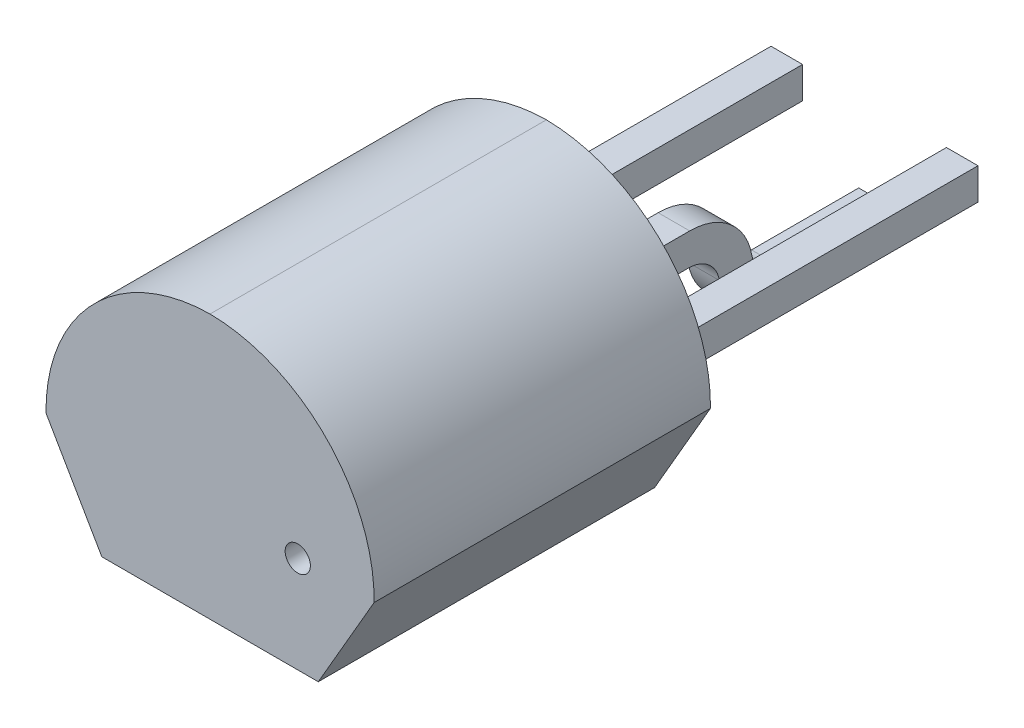
SolidWorks part; units mm, degrees
ref_plane "Спереди" through (0, 0, 0) normal (0, 0, 1) x (1, 0, 0)
ref_plane "Сверху" through (0, 0, 0) normal (0, 1, 0) x (1, 0, 0)
ref_plane "Справа" through (0, 0, 0) normal (1, 0, 0) x (0, 0, -1)
sketch "Эскиз1" plane through (0, 0, 0) normal (0, 0, 1) x (1, 0, 0)
  line L0 (1.14, 0.25) -> (1.64, 0.25)
  line L1 (-0.25, 0.25) -> (0.25, 0.25)
  line L2 (-0.25, 0.25) -> (-0.25, -0.25)
  line L3 (-0.25, -0.25) -> (0.25, -0.25)
  line L4 (0.25, 0.25) -> (0.25, -0.25)
  line L5 (1.14, 0.25) -> (1.14, -0.25)
  line L6 (1.14, -0.25) -> (1.64, -0.25)
  line L7 (1.64, 0.25) -> (1.64, -0.25)
  line L8 (2.53, 0.25) -> (3.03, 0.25)
  line L9 (2.53, 0.25) -> (2.53, -0.25)
  line L10 (2.53, -0.25) -> (3.03, -0.25)
  line L11 (3.03, 0.25) -> (3.03, -0.25)
  line L12 (1.39, 0.25) -> (1.39, -1.8309) construction
  dimension "D1" = 0.5
  dimension "D2" = 0.5
  dimension "D3" = 1.39
ref_plane "Плоскость1" through (0, 0, 2.54) normal (0, 0, 1) x (1, 0, 0)
sketch "Эскиз3" plane through (0, 0, 2.54) normal (0, 0, 1) x (1, 0, 0)
  line L0 (-0.325, -1.53) -> (3.105, -1.53)
  line L6 (-1.21, 0) -> (-0.325, -1.53)
  line L7 (3.99, 0) -> (3.105, -1.53)
  arc A0 (-1.21, 0) -> (1.39, 2.66) centre (1.42, 0.03) cw
  arc A1 (1.39, 2.66) -> (3.99, 0) centre (1.36, 0.03) cw
  dimension "D3" = 2.6302
  dimension "D4" = 2.6302
  dimension "D1" = 5.2
  dimension "D2" = 4.19
  dimension "D5" = 3.43
  dimension "D6" = 1.21
  dimension "D7" = 120.046
extrude "Вытянуть1" add sketch "Эскиз3" along normal blind 5.33
extrude "Вытянуть2" add sketch "Эскиз1" along normal blind 2.54
extrude "Вытянуть3" add sketch "Эскиз1<2>" against normal blind 10.16
sketch "Эскиз1<2>" plane through (0, 0, 0) normal (0, 0, 1) x (1, 0, 0) same geometry as "Эскиз1"
sketch "Эскиз4" plane through (0, 0, 7.87) normal (0, 0, 1) x (1, 0, 0)
  line L0 (1.39, 3.1548) -> (1.39, -1.9485) construction
  line L1 (-1.21, 0) -> (-0.325, -1.53) construction
  line L2 (3.105, -1.53) -> (3.99, 0) construction
  circle A1 centre (2.78, 0) radius 0.2
extrude "Вырез-Вытянуть1" cut sketch "Эскиз4" against normal blind 0.5
sketch "Эскиз5" plane through (0, -0.25, 0) normal (0, 1, 0) x (1, 0, 0)
  line L0 (1.14, -0.04) -> (1.64, -0.04)
  line L4 (1.64, -2.54) -> (1.64, 10.16)
  line L5 (1.64, 10.16) -> (1.14, 10.16)
  line L6 (1.14, 10.16) -> (1.14, -2.54)
  line L7 (1.14, -2.54) -> (1.64, -2.54)
  line L8 (1.64, -0.04) -> (1.64, 10.16)
  line L9 (1.64, 10.16) -> (1.14, 10.16)
  line L10 (1.14, 10.16) -> (1.14, -0.04)
  dimension "D1" = 0
extrude "Вытянуть4" add sketch "Эскиз5" against normal blind 1.25
sketch "Эскиз6" plane through (1.64, 0, 0) normal (1, 0, 0) x (0, 0, -1)
  line L1 (2.46, -1) -> (10.7871, -1)
  line L2 (2.46, -1) -> (0.96, -1)
  line L3 (10.16, -1.5) -> (-0.04, -1.5) construction
  line L4 (10.7871, -1) -> (10.7871, 0.8385)
  line L5 (0.46, -0.5) -> (0.46, 2.1254)
  line L7 (0.46, 2.1254) -> (2.46, 2.1254)
  line L8 (2.46, 2.1254) -> (10.7871, 2.1254)
  line L9 (10.7871, 2.1254) -> (10.7871, 0.8385)
  arc A1 (0.96, -1) -> (0.46, -0.5) centre (0.96, -0.5) cw
  dimension "D2" = 0.5
  dimension "D1" = 0.5
extrude "Вырез-Вытянуть2" cut sketch "Эскиз6" against normal blind 1
fillet "Скругление1" radius 0.5 1 edges at (1.39, -0.25, 0.04)
fillet "Скругление2" radius 1 2 edges at (1.39, -1.5, 0.04) (1.39, 0.25, -0.46)
sketch "Эскиз7" plane through (0, 0, -10.16) normal (0, 0, -1) x (-1, 0, 0)
  line L4 (-1.14, -1.5) -> (-1.14, -1)
  line L5 (-1.14, -1) -> (-1.64, -1)
  line L6 (-1.64, -1) -> (-1.64, -1.5)
  line L7 (-1.64, -1.5) -> (-1.14, -1.5)
  line L8 (-1.14, -1.5) -> (-1.14, -1)
  line L9 (-1.14, -1) -> (-1.64, -1)
  line L10 (-1.64, -1) -> (-1.64, -1.5)
  line L11 (-1.64, -1.5) -> (-1.14, -1.5)
  line L12 (0.25, -0.25) -> (0.25, 0.25)
  line L13 (0.25, 0.25) -> (-0.25, 0.25)
  line L14 (-0.25, 0.25) -> (-0.25, -0.25)
  line L15 (-0.25, -0.25) -> (0.25, -0.25)
  line L16 (0.25, -0.25) -> (0.25, 0.25)
  line L17 (0.25, 0.25) -> (-0.25, 0.25)
  line L18 (-0.25, 0.25) -> (-0.25, -0.25)
  line L19 (-0.25, -0.25) -> (0.25, -0.25)
  line L20 (-2.53, -0.25) -> (-2.53, 0.25)
  line L21 (-2.53, 0.25) -> (-3.03, 0.25)
  line L22 (-3.03, 0.25) -> (-3.03, -0.25)
  line L23 (-3.03, -0.25) -> (-2.53, -0.25)
  line L24 (-2.53, -0.25) -> (-2.53, 0.25)
  line L25 (-2.53, 0.25) -> (-3.03, 0.25)
  line L26 (-3.03, 0.25) -> (-3.03, -0.25)
  line L27 (-3.03, -0.25) -> (-2.53, -0.25)
  dimension "D1" = 0
  dimension "D2" = 0
  dimension "D3" = 0
extrude "Вырез-Вытянуть3" cut sketch "Эскиз7" against normal blind 7.5
sketch "Эскиз8" plane through (0, 0, -2.66) normal (0, 0, -1) x (-1, 0, 0)
  line L0 (-1.14, -1) -> (-1.64, -1) construction
  line L1 (-1.14, -1.5) -> (-1.14, -1) construction
  circle A0 centre (-1.39, -1.25) radius 0.1245
  dimension "D1" = 0.25
  dimension "D2" = 0.25
extrude "Вырез-Вытянуть4" cut sketch "Эскиз8" against normal blind 1
